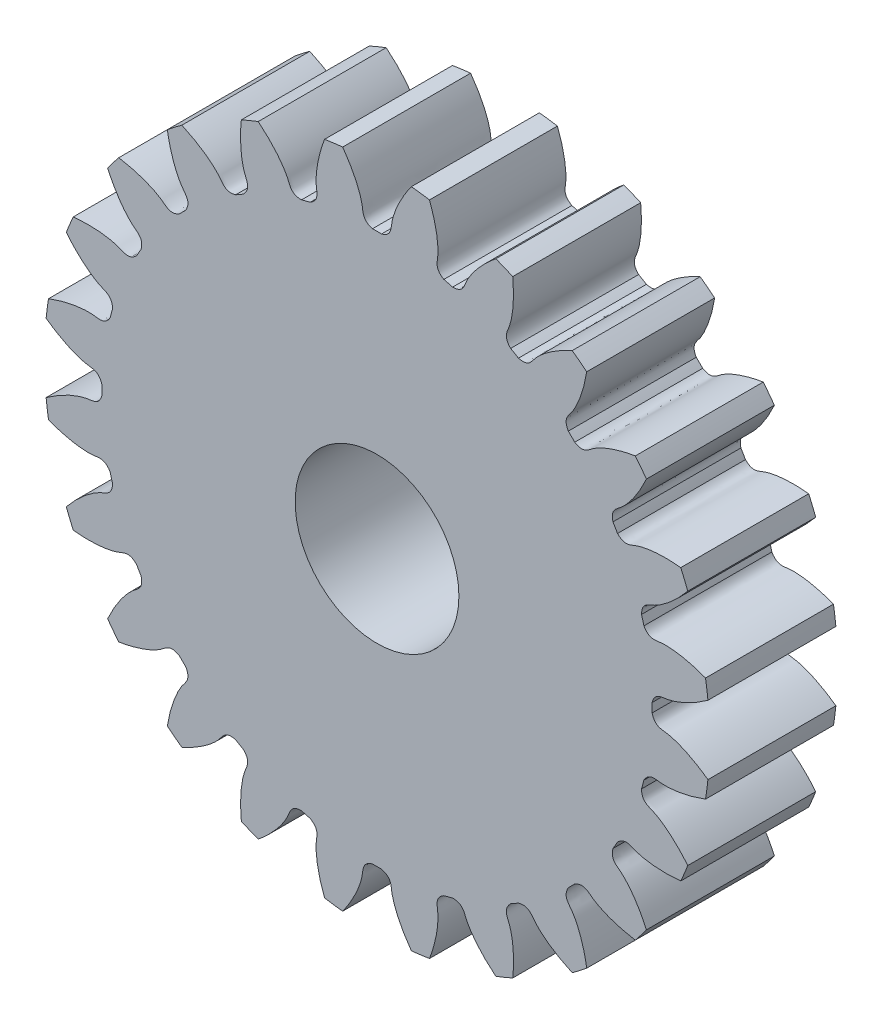
SolidWorks part; units mm, degrees
ref_plane "前视基准面" through (0, 0, 0) normal (0, 0, 1) x (1, 0, 0)
ref_plane "上视基准面" through (0, 0, 0) normal (0, 1, 0) x (1, 0, 0)
ref_plane "右视基准面" through (0, 0, 0) normal (1, 0, 0) x (0, 0, -1)
other "Configuration Table"
sketch "草图1" plane through (0, 0, 0) normal (0, 0, 1) x (1, 0, 0)
  circle A0 centre (0, 0) radius 6.5
extrude "凸台-拉伸1" add sketch "草图1" along normal blind 2.5
ref_axis "基准轴1" through (0, 0, 2.5) along (0, 0, -1)
sketch "草图2" plane through (0, 0, 0) normal (0, 0, 1) x (1, 0, 0)
  line L0 (0, 0) -> (0, 6.5) construction
  circle A0 centre (0, 0) radius 6.5 construction
  arc A1 (0.0884, 5.3743) -> (-0.0884, 5.3743) centre (0, 0) ccw
  arc A2 (1.5578, 7.3471) -> (-1.5578, 7.3471) centre (0, 0) ccw
  spline S0 degree 3 poles (0.0884, 5.3743) (0.284, 5.4284) (0.2695, 5.5579) (0.2931, 5.6863) (0.2965, 5.7029) (0.3007, 5.7216) (0.3058, 5.7424) (0.312, 5.7653) (0.3191, 5.7902) (0.3275, 5.8171) (0.3371, 5.846) (0.348, 5.8769) (0.3604, 5.9096) (0.3742, 5.9441) (0.3896, 5.9805) (0.4067, 6.0185) (0.4254, 6.0583) (0.446, 6.0997) (0.4684, 6.1427) (0.4928, 6.1872) (0.5192, 6.2332) (0.5476, 6.2806) (0.5782, 6.3293) (0.611, 6.3792) (0.6461, 6.4304) (0.6834, 6.4827) (0.7232, 6.536) (0.7654, 6.5903) (0.8101, 6.6456) (0.8574, 6.7016) (0.9073, 6.7583) (0.9598, 6.8158) (1.015, 6.8738) (1.0729, 6.9322) (1.1336, 6.9911) (1.1972, 7.0503) (1.2635, 7.1097) (1.3328, 7.1693) (1.4302, 7.2497) (1.506, 7.3084) (1.5578, 7.3471) knots 0 0 0 0 0.143961 0.149818 0.156577 0.164236 0.172796 0.182258 0.19262 0.203884 0.216049 0.229115 0.243082 0.25795 0.273719 0.290389 0.30796 0.326433 0.345806 0.366081 0.387257 0.409333 0.432311 0.45619 0.48097 0.506651 0.533234 0.560717 0.589101 0.618387 0.648574 0.679661 0.71165 0.74454 0.778331 0.813023 0.848616 0.885111 0.922506 1 1 1 1
  spline S1 degree 3 poles (-0.0884, 5.3743) (-0.284, 5.4284) (-0.2695, 5.5579) (-0.2931, 5.6863) (-0.2965, 5.7029) (-0.3007, 5.7216) (-0.3058, 5.7424) (-0.312, 5.7653) (-0.3191, 5.7902) (-0.3275, 5.8171) (-0.3371, 5.846) (-0.348, 5.8769) (-0.3604, 5.9096) (-0.3742, 5.9441) (-0.3896, 5.9805) (-0.4067, 6.0185) (-0.4254, 6.0583) (-0.446, 6.0997) (-0.4684, 6.1427) (-0.4928, 6.1872) (-0.5192, 6.2332) (-0.5476, 6.2806) (-0.5782, 6.3293) (-0.611, 6.3792) (-0.6461, 6.4304) (-0.6834, 6.4827) (-0.7232, 6.536) (-0.7654, 6.5903) (-0.8101, 6.6456) (-0.8574, 6.7016) (-0.9073, 6.7583) (-0.9598, 6.8158) (-1.015, 6.8738) (-1.0729, 6.9322) (-1.1336, 6.9911) (-1.1972, 7.0503) (-1.2635, 7.1097) (-1.3328, 7.1693) (-1.4302, 7.2497) (-1.506, 7.3084) (-1.5578, 7.3471) knots 0 0 0 0 0.143961 0.149818 0.156577 0.164236 0.172796 0.182258 0.19262 0.203884 0.216049 0.229115 0.243082 0.25795 0.273719 0.290389 0.30796 0.326433 0.345806 0.366081 0.387257 0.409333 0.432311 0.45619 0.48097 0.506651 0.533234 0.560717 0.589101 0.618387 0.648574 0.679661 0.71165 0.74454 0.778331 0.813023 0.848616 0.885111 0.922506 1 1 1 1
extrude "切除-拉伸1" cut sketch "草图2" along normal through all
pattern_circular "阵列(圆周)1" count 24 every 15 about axis through (0, 0, 2.5) along (0, 0, -1) of "切除-拉伸1"
sketch "草图3" plane through (0, 0, 0) normal (0, 0, 1) x (1, 0, 0)
  circle A0 centre (0, 0) radius 6 construction
  dimension "Dn" = 12
sketch "草图4" plane through (0, 0, 2.5) normal (0, 0, 1) x (1, 0, 0)
  circle A0 centre (0, 0) radius 1.6
  dimension "D1" = 3.2
extrude "切除-拉伸2" cut sketch "草图4" against normal mid plane 10
